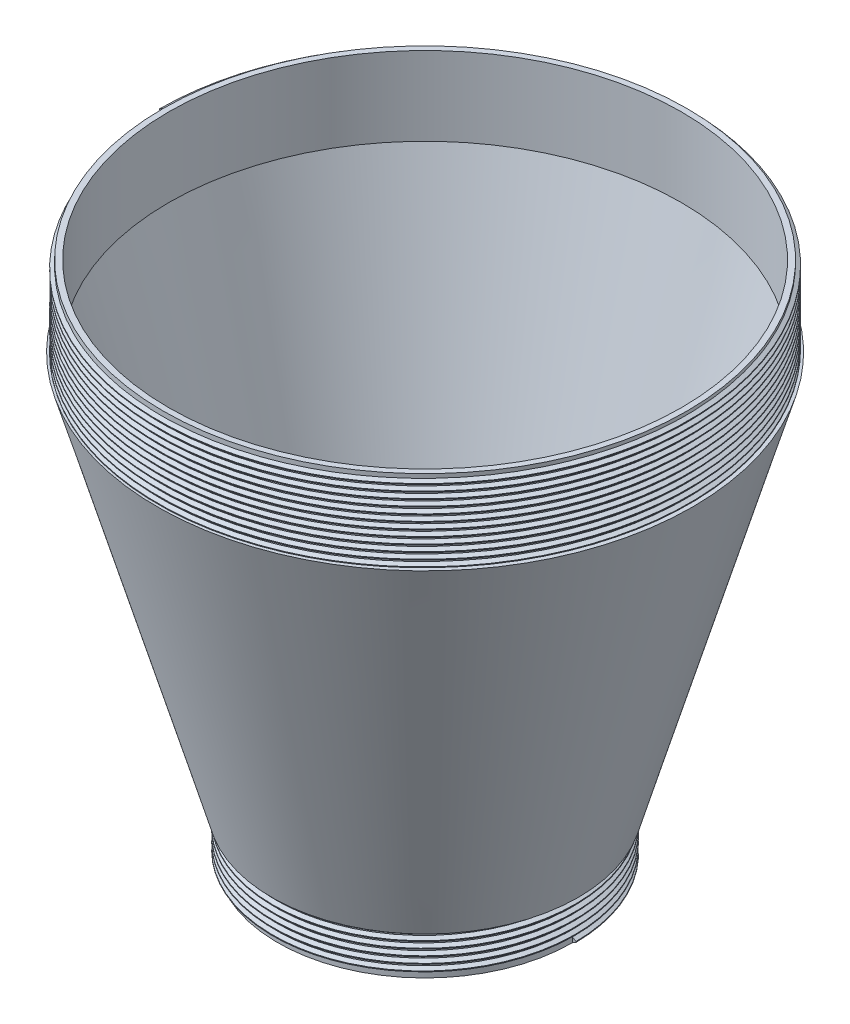
SolidWorks part; units mm, degrees
material "ABS PC"
ref_plane "Front Plane" through (0, 0, 0) normal (0, 0, 1) x (1, 0, 0)
ref_plane "Top Plane" through (0, 0, 0) normal (0, 1, 0) x (1, 0, 0)
ref_plane "Right Plane" through (0, 0, 0) normal (1, 0, 0) x (0, 0, -1)
sketch "Sketch1" plane through (0, 0, 0) normal (0, 0, 1) x (1, 0, 0)
  line L0 (0, -1000) -> (0, 49000) construction
  line L12 (-35.1, -40.0417) -> (-61.3, 50.5173)
  line L26 (-35.1, -40.0417) -> (-68.3675, 74.9459) construction
  line L27 (-32.5, -39.6731) -> (-64.9087, 72.3459) construction
  line L29 (-32.5, -39.6731) -> (-58.7, 50.8859)
  line L31 (-32.5, -73.891) -> (-32.5, -39.6731) construction
  line L36 (-68.3675, 74.9459) -> (-35, 74.9459) construction
  line L37 (-64.9087, 72.3459) -> (-35, 72.3459) construction
  line L41 (-2.9583, -72.5541) -> (-32.5, -72.5541) construction
  line L42 (-0.0924, -75.1541) -> (-32.5, -75.1541) construction
  line L43 (-1.2805, -62.9707) -> (-0.0924, -75.1541) construction
  line L44 (-32.5, -73.891) -> (-1.2805, -62.9707) construction
  line L45 (-35.1, -77.555) -> (-35.1, -40.0417) construction
  line L46 (-35.1, -77.555) -> (-3.547, -66.5179) construction
  line L50 (-3.547, -66.5179) -> (-2.9583, -72.5541) construction
  line L53 (-32.5, -39.7088) -> (-32.5, -49.7088)
  line L54 (-32.5, -49.7088) -> (-33.75, -49.7088)
  line L55 (-33.75, -49.7088) -> (-33.75, -40.0343)
  line L56 (-33.75, -40.0343) -> (-35.1, -40.0343)
  line L57 (-35.1, -40.0343) -> (-35.1, -40.0417)
  line L58 (-32.5, -39.7088) -> (-32.5, -39.6731)
  line L59 (-58.7, 50.8859) -> (-58.7, 68.8859)
  line L60 (-61.3, 50.5173) -> (-60, 50.5173)
  line L62 (-60, 68.8859) -> (-58.7, 68.8859)
  line L63 (-60, 50.5173) -> (-60, 68.8859)
  dimension "D5" = 2.6
  dimension "D1" = 32.5
  dimension "D6" = 1.25
  dimension "D7" = 60
  dimension "D2" = 10
  dimension "D3" = 2.6
  dimension "D4" = 2.6
  dimension "D8" = 18
  dimension "D9" = 1.3
revolve "Revolve1" add sketch "Sketch1" angle 360 about L0
thread "Thread1" pitch 1.5 method extrude profile "Thread Profile1" start angle 0, offset 0, length 0, pitch 1.5, diameter 67.5
ref_plane "Plane1" through (33.75, -49.7088, 0) normal (0, 0, 1) x (1, 0, 0)
sketch "Thread Profile1" plane through (33.75, -49.7088, 0) normal (0, 0, 1) x (1, 0, 0)
  line L0 (0, 0) -> (0, 1.5) construction
  line L1 (0, 0) -> (0.8119, 0.4687)
  line L2 (0.8119, 0.4687) -> (0.8119, 0.6562)
  line L3 (0.8119, 0.6562) -> (0, 1.125)
  line L4 (0.8119, 0.5625) -> (0, 0.5625) construction
  line L11 (0, 0) -> (0, 1.125)
  point P2 (0, 0)
  dimension "Pitch" = 1.5
  dimension "Profile_Angle" = 60
  dimension "Profile_Land" = 0.1875
  dimension "Profile_Height" = 0.8119
thread "Thread2" pitch 1.5 method extrude profile "Thread Profile2" start angle 0, offset 0, length 0, pitch 1.5, diameter 120
ref_plane "Plane2" through (-60, 68.8859, 0) normal (0, 0, 1) x (-1, 0, 0)
sketch "Thread Profile2" plane through (-60, 68.8859, 0) normal (0, 0, 1) x (-1, 0, 0)
  line L0 (0, 0) -> (0, 1.5) construction
  line L1 (0, 0) -> (0.8119, 0.4687)
  line L2 (0.8119, 0.4687) -> (0.8119, 0.6562)
  line L3 (0.8119, 0.6562) -> (0, 1.125)
  line L4 (0.8119, 0.5625) -> (0, 0.5625) construction
  line L11 (0, 0) -> (0, 1.125)
  point P2 (0, 0)
  dimension "Pitch" = 1.5
  dimension "Profile_Angle" = 60
  dimension "Profile_Land" = 0.1875
  dimension "Profile_Height" = 0.8119
